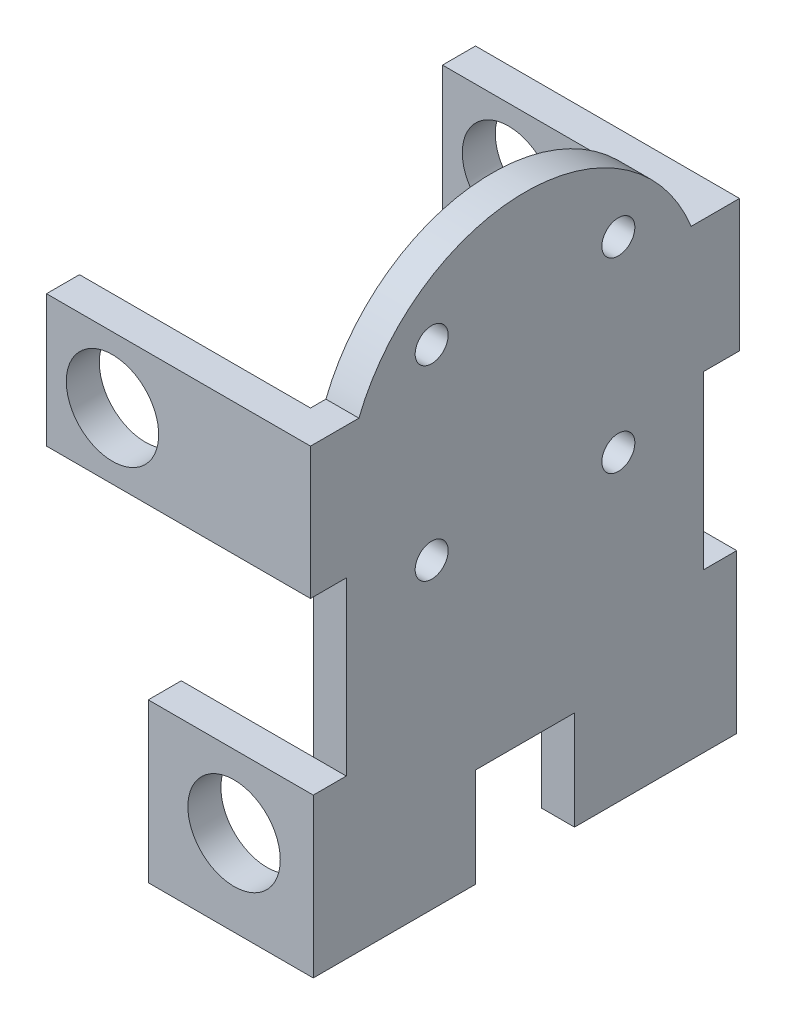
SolidWorks part; units mm, degrees
ref_plane "Front Plane" through (0, 0, 0) normal (0, 0, 1) x (1, 0, 0)
ref_plane "Top Plane" through (0, 0, 0) normal (0, 1, 0) x (1, 0, 0)
ref_plane "Right Plane" through (0, 0, 0) normal (1, 0, 0) x (0, 0, -1)
sketch "Sketch1" plane through (0, 0, 0) normal (1, 0, 0) x (0, 0, -1)
  line L0 (-27.08, 0) -> (-27.08, -60)
  line L1 (27.08, 0) -> (27.08, -60)
  line L2 (-27.08, -60) -> (27.08, -60)
  arc A0 (-27.08, 0) -> (27.08, 0) centre (0, 0) cw
  dimension "D1" = 27.08
  dimension "D2" = 60
extrude "Boss-Extrude1" add sketch "Sketch1" along normal blind 2.5 and the other way blind 2.5
sketch "Sketch2" plane through (2.5, 0, 0) normal (1, 0, 0) x (0, 0, -1)
  line L0 (0, 0) -> (0, 20) construction
  line L1 (0, 0) -> (-14.1421, 14.1421) construction
  circle A0 centre (0, 0) radius 20 construction
  circle A1 centre (-14.1421, 14.1421) radius 2.5
  circle A2 centre (14.1421, 14.1421) radius 2.5
  circle A3 centre (14.1421, -14.1421) radius 2.5
  circle A4 centre (-14.1421, -14.1421) radius 2.5
  point P15 (0, 0)
  dimension "D1" = 5
  dimension "D3" = 40
  dimension "D2" = 45
  dimension "D4" = 4
extrude "Cut-Extrude1" cut sketch "Sketch2" against normal through all
sketch "Sketch3" plane through (0, 0, 0) normal (1, 0, 0) x (0, 0, -1)
  line L1 (-32.5, 10) -> (32.5, 10)
  line L2 (-32.5, 10) -> (-32.5, -10)
  line L3 (-32.5, -10) -> (32.5, -10)
  line L4 (32.5, 10) -> (32.5, -10)
  point P4 (0, 10)
  point P6 (-32.5, 0)
  dimension "D1" = 20
  dimension "D2" = 65
extrude "Boss-Extrude2" add sketch "Sketch3" along normal blind 2.5 and the other way blind 2.5
sketch "Sketch5" plane through (-2.5, 0, 0) normal (-1, 0, 0) x (0, 0, 1)
  line L0 (-27.08, -10) -> (-32.5, -10) construction
  line L1 (-32.5, 10) -> (-27.5, 10)
  line L2 (-32.5, 10) -> (-32.5, -10)
  line L3 (-32.5, -10) -> (-27.5, -10)
  line L4 (-27.5, 10) -> (-27.5, -10)
  line L5 (32.5, -10) -> (27.08, -10) construction
  line L6 (32.5, 10) -> (27.5, 10)
  line L7 (32.5, 10) -> (32.5, -10)
  line L8 (32.5, -10) -> (27.5, -10)
  line L9 (27.5, 10) -> (27.5, -10)
  dimension "D1" = 5
extrude "Boss-Extrude4" add sketch "Sketch5" along normal blind 35
sketch "Sketch6" plane through (0, 0, -32.5) normal (0, 0, -1) x (-1, 0, 0)
  line L0 (37.5, 10) -> (37.5, -10) construction
  circle A0 centre (27.5, 0) radius 7
  dimension "D1" = 14
  dimension "D2" = 10
extrude "Cut-Extrude2" cut sketch "Sketch6" against normal through all
sketch "Sketch7" plane through (-2.5, 0, 0) normal (-1, 0, 0) x (0, 0, 1)
  line L0 (27.08, -60) -> (-27.08, -60) construction
  line L2 (7.5, -60) -> (-7.5, -60)
  line L3 (7.5, -60) -> (7.5, -45)
  line L4 (7.5, -45) -> (-7.5, -45)
  line L5 (-7.5, -60) -> (-7.5, -45)
  point P6 (0, -45)
  dimension "D1" = 15
  dimension "D2" = 15
extrude "Cut-Extrude3" cut sketch "Sketch7" against normal through all
sketch "Sketch8" plane through (0, 0, 27.08) normal (0, 0, 1) x (1, 0, 0)
  line L1 (2.5, -60) -> (-22.5, -60)
  line L2 (2.5, -60) -> (2.5, -36)
  line L3 (2.5, -36) -> (-22.5, -36)
  line L4 (-22.5, -60) -> (-22.5, -36)
  dimension "D1" = 24
  dimension "D2" = 25
extrude "Boss-Extrude5" add sketch "Sketch8" along normal blind 5
mirror "Mirror1" about plane through (0, 0, 0) normal (0, 0, 1) of "Boss-Extrude5"
sketch "Sketch9" plane through (0, 0, 27.08) normal (0, 0, -1) x (-1, 0, 0)
  line L0 (2.5, -60) -> (2.5, -36) construction
  line L1 (2.5, -36) -> (22.5, -36) construction
  circle A0 centre (9.5, -47) radius 7
  dimension "D1" = 14
  dimension "D2" = 11
extrude "Cut-Extrude4" cut sketch "Sketch9" against normal through all and the other way through all
